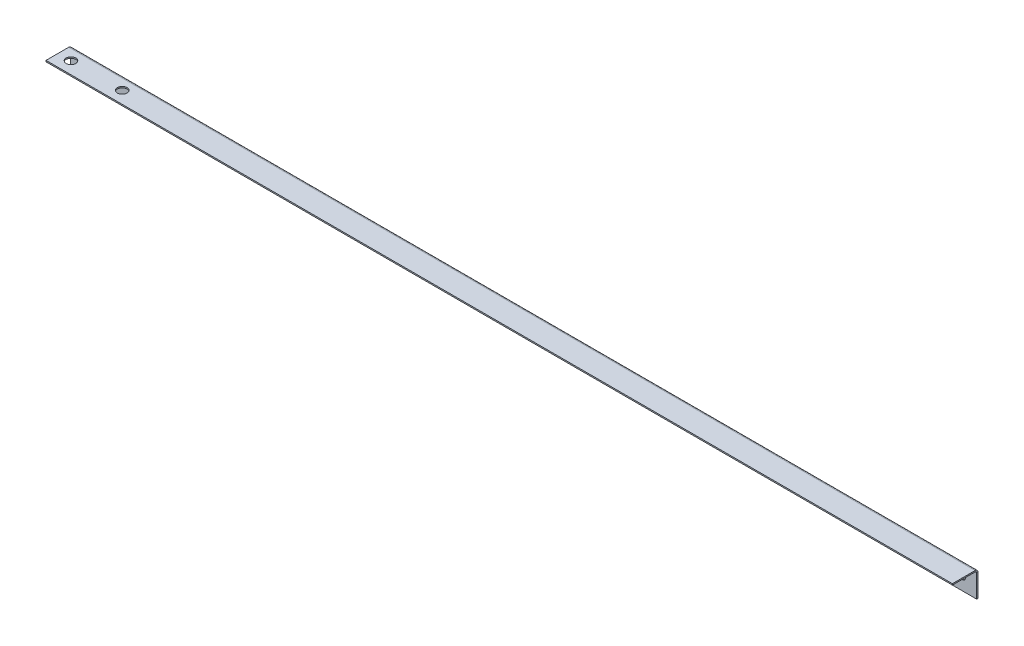
SolidWorks part; units mm, degrees
note: The reader was unsure of these and kept them because the rebuilt part matched: flange length of "Edge-Flange1".
material "ASTM A36 Steel"
ref_plane "Front Plane" through (0, 0, 0) normal (0, 0, 1) x (1, 0, 0)
ref_plane "Top Plane" through (0, 0, 0) normal (0, 1, 0) x (1, 0, 0)
ref_plane "Right Plane" through (0, 0, 0) normal (1, 0, 0) x (0, 0, -1)
sketch "Sketch1" plane through (0, 0, 0) normal (0, 0, 1) x (1, 0, 0)
  line L0 (474.5557, 62.8577) -> (459.5557, 62.8577) construction
  line L1 (497.0557, 82.8577) -> (-917.9443, 82.8577)
  line L2 (497.0557, 82.8577) -> (497.0557, 42.8577)
  line L3 (497.0557, 42.8577) -> (-917.9443, 42.8577)
  line L4 (-917.9443, 82.8577) -> (-917.9443, 42.8577)
  line L5 (474.5557, 57.8577) -> (459.5557, 57.8577)
  line L6 (474.5557, 67.8577) -> (459.5557, 67.8577)
  line L7 (374.5557, 62.8577) -> (359.5557, 62.8577) construction
  line L8 (374.5557, 57.8577) -> (359.5557, 57.8577)
  line L9 (374.5557, 67.8577) -> (359.5557, 67.8577)
  arc A0 (474.5557, 57.8577) -> (474.5557, 67.8577) centre (474.5557, 62.8577) ccw
  arc A1 (459.5557, 67.8577) -> (459.5557, 57.8577) centre (459.5557, 62.8577) ccw
  arc A2 (374.5557, 57.8577) -> (374.5557, 67.8577) centre (374.5557, 62.8577) ccw
  arc A3 (359.5557, 67.8577) -> (359.5557, 57.8577) centre (359.5557, 62.8577) ccw
  point P6 (467.0557, 62.8577)
  point P11 (367.0557, 62.8577)
  dimension "D3" = 15
  dimension "D1" = 1415
  dimension "D2" = 40
  dimension "D4" = 30
  dimension "D5" = 10
  dimension "D6" = 15
  dimension "D7" = 100
  dimension "D8" = 20
base flange "Base-Flange1" sketch "Sketch1" thickness 2 reverse thickness direction no parameters "D1"=2.5
edge flange "Edge-Flange1" sketch "Sketch8" flange angle 90 flange length 40 flange position material inside bend radius 2.5 thickness 2 relief rectangular parameters "D6"=10
sketch "Sketch8" plane through (0, 82.8577, 0) normal (0, -1, 0) x (1, 0, 0)
  line L1 (497.0557, 0) -> (-917.9443, 0) construction
  line L2 (-917.9443, 0) -> (-917.9443, 38)
  line L3 (-917.9443, 38) -> (497.0557, 38)
  line L4 (497.0557, 38) -> (497.0557, 0)
  line L5 (497.0557, 0) -> (-917.9443, 0)
bend "EdgeBend1" bend radius 2.5 bend angle 90 parameters "D5"=1
sketch "Sketch9" plane through (0, 80.8577, 0) normal (0, -1, 0) x (1, 0, 0)
  line L0 (-917.9443, 38) -> (-917.9443, 2.5) construction
  circle A0 centre (-897.9443, 19) radius 7.5
  circle A1 centre (-817.9443, 19) radius 7.5
  dimension "D1" = 20
  dimension "D2" = 80
  dimension "D3" = 15
  dimension "D4" = 15
extrude "Cut-Extrude1" cut sketch "Sketch9" against normal through all normal cut yes
sketch "Bend-Lines1" [suppressed] plane through (0, 0, 0) normal (0, 1, 0) x (1, 0, 0)
sketch "Bounding-Box1" [suppressed] plane through (0, 0, 0) normal (0, 1, 0) x (1, 0, 0)
sheet metal parameters "Sheet-Metal1" thickness 2 parameters "D1"=2.5
flat pattern "Flat-Pattern1" [suppressed]
sketch "Bend-Lines2" plane through (0, 0, 0) normal (0, 1, 0) x (1, 0, 0)
sketch3d "Bounding-Box2" [suppressed]
  line L0 (667.9443, 42.8577, 0) -> (-497.0557, 42.8577, 0) construction
  line L1 (667.9443, 82.8577, 0) -> (-497.0557, 82.8577, 0) construction
  line L2 (667.9443, 42.8577, 0) -> (667.9443, 82.8577, 0) construction
  line L3 (-497.0557, 42.8577, 0) -> (-497.0557, 82.8577, 0) construction
sheet metal parameters "Sheet-Metal2" thickness 2 parameters "D1"=2.5
flat pattern "Flat-Pattern1"
sketch "Bend-Lines2" plane through (0, 0, 0) normal (0, 0, 1) x (1, 0, 0)
  line L0 (497.0557, 81.1066) -> (-667.9443, 81.1066) construction
  line L1 (497.0557, 81.1066) -> (-667.9443, 81.1066) construction
sketch3d "Bounding-Box2" [suppressed]
  line L0 (-667.9443, 42.8577, 0) -> (497.0557, 42.8577, 0) construction
  line L1 (-667.9443, 119.3555, 0) -> (497.0557, 119.3555, 0) construction
  line L2 (-667.9443, 42.8577, 0) -> (-667.9443, 119.3555, 0) construction
  line L3 (497.0557, 42.8577, 0) -> (497.0557, 119.3555, 0) construction
bend of the flat pattern "Flatten-<EdgeBend1>1"
sheet metal parameters "Sheet-Metal3" thickness 2 parameters "D1"=2.5
flat pattern "Flat-Pattern1"
sketch "Bend-Lines2" plane through (0, 0, 0) normal (0, 0, 1) x (1, 0, 0)
  line L0 (497.0557, 81.1066) -> (-917.9443, 81.1066) construction
  line L1 (497.0557, 81.1066) -> (-917.9443, 81.1066) construction
sketch3d "Bounding-Box2" [suppressed]
  line L0 (-917.9443, 42.8577, 0) -> (497.0557, 42.8577, 0) construction
  line L1 (-917.9443, 119.3555, 0) -> (497.0557, 119.3555, 0) construction
  line L2 (-917.9443, 42.8577, 0) -> (-917.9443, 119.3555, 0) construction
  line L3 (497.0557, 42.8577, 0) -> (497.0557, 119.3555, 0) construction
bend of the flat pattern "Flatten-<EdgeBend1>1"
